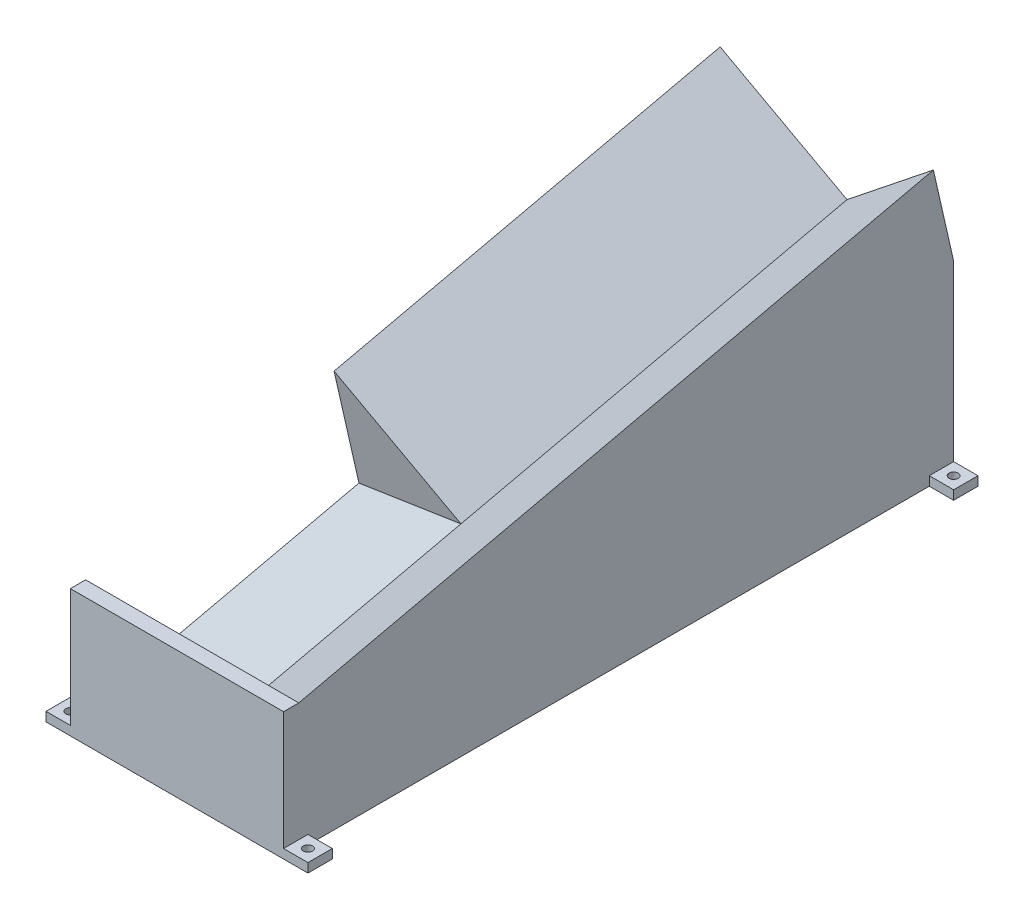
SolidWorks part; units mm, degrees
note: The reader was unsure of these and kept them because the rebuilt part matched: shared geometry of "Sketch4<3>".
ref_plane "Front Plane" through (0, 0, 0) normal (0, 0, 1) x (1, 0, 0)
ref_plane "Top Plane" through (0, 0, 0) normal (0, 1, 0) x (1, 0, 0)
ref_plane "Right Plane" through (0, 0, 0) normal (1, 0, 0) x (0, 0, -1)
sketch "Sketch3" plane through (0, 0, 0) normal (1, 0, 0) x (0, 0, -1)
  line L0 (38.5, 0) -> (-38.5, 0) construction
  line L1 (0, 0) -> (220, 0)
  line L2 (0, 0) -> (0, 10)
  line L3 (0, 10) -> (220, 10)
  line L4 (220, 0) -> (220, 10)
  line L5 (220, 10) -> (220, 60)
  line L6 (220, 60) -> (0, 10)
  line L7 (0, 38.5) -> (0, -38.5) construction
  point P6 (70, 41.2989)
  dimension "D1" = 10
  dimension "D2" = 220
  dimension "D3" = 0
  dimension "D4" = 50
extrude "Boss-Extrude2" add sketch "Sketch3" along normal blind 70 contours L5 L6 L3 | L1 L4 L3 L2
ref_plane "Plane1" through (0, 50.4912, -222.1611) normal (0, 0.2216, -0.9751) x (-1, 0, 0)
sketch "Sketch4" plane through (0, 50.4912, -222.1611) normal (0, 0.2216, -0.9751) x (-1, 0, 0)
  line L0 (-70, 9.7513) -> (-70, 39.7513)
  line L1 (-70, 39.7513) -> (-35, 9.7513)
  line L2 (-70, 9.7513) -> (0, 9.7513) construction
  line L3 (-35, 9.7513) -> (0, 39.7513)
  line L4 (0, 49.0074) -> (0, -49.0074) construction
  line L5 (0, 39.7513) -> (0, 9.7513)
  line L6 (-70, 9.7513) -> (0, 9.7513)
  dimension "D1" = 30
extrude "Boss-Extrude3" add sketch "Sketch4" against normal blind 130 contours L0 L6 L1 | L3 L6 L5
extrude "Boss-Extrude4" add sketch "Sketch4<3>" against normal blind 225 contours L0 L6 L1
sketch "Sketch4<3>" plane through (0, 50.4912, -222.1611) normal (0, 0.2216, -0.9751) x (-1, 0, 0) same geometry as "Sketch4"
sketch "Sketch7" plane through (0, 0, 0) normal (-1, 0, 0) x (0, 0, 1)
  line L0 (0, 3) -> (-220, 53) construction
  line L1 (-220, 0) -> (-220, 60) construction
  line L2 (-86.5841, 60.4432) -> (-213.3514, 89.254) construction
  line L3 (0, -38.5) -> (0, 38.5) construction
  line L4 (38.5, 0) -> (-38.5, 0) construction
  point P7 (0, 3.0122)
  dimension "D1" = 3
sketch "Sketch8" plane through (0, 50.4912, -222.1611) normal (0, 0.2216, -0.9751) x (-1, 0, 0)
  line L0 (-35, 9.7513) -> (0, 2.9254)
  line L1 (-35, 9.7513) -> (0, 9.7513)
  line L2 (0, 49.0897) -> (0, -49.0897) construction
  line L3 (-35, 9.7513) -> (0, 9.7513) construction
  line L4 (0, 9.7513) -> (0, 2.9254)
extrude "Cut-Extrude1" cut sketch "Sketch8" along normal up to surface (95.6103 mm away) from surface
sketch "Sketch9" plane through (0, 0, 0) normal (-1, 0, 0) x (0, 0, 1)
  line L0 (6.0535, 39.3892) -> (-213.3514, 89.254) construction
  line L1 (0, 0) -> (-5, 0)
  line L2 (0, 0) -> (0, 41.9014)
  line L3 (0, 41.9014) -> (-5, 41.9014)
  line L4 (-5, 0) -> (-5, 41.9014)
  dimension "D1" = 5
extrude "Boss-Extrude5" add sketch "Sketch9" against normal up to surface (70 mm away) up to face at (70, 29.8255, -92.5561)
sketch "Sketch10" plane through (0, 0, 0) normal (-1, 0, 0) x (0, 0, 1)
  line L1 (0, 0) -> (13.7086, 0)
  line L2 (0, 0) -> (0, 41.9495)
  line L3 (0, 41.9495) -> (13.7086, 41.9495)
  line L4 (13.7086, 0) -> (13.7086, 41.9495)
extrude "Cut-Extrude2" cut sketch "Sketch10" against normal through all
sketch "Sketch11" plane through (0, 0, 0) normal (0, 1, 0) x (1, 0, 0)
  line L0 (0, 0) -> (0, 220) construction
  line L1 (0, 220) -> (-8, 220)
  line L2 (0, 220) -> (0, 212)
  line L3 (0, 212) -> (-8, 212)
  line L4 (-8, 220) -> (-8, 212)
  line L5 (35, 220) -> (0, 220) construction
  line L6 (78, 220) -> (70, 220)
  line L7 (78, 220) -> (78, 212)
  line L8 (78, 212) -> (70, 212)
  line L9 (70, 220) -> (70, 212)
  line L10 (0, 8) -> (-8, 8)
  line L11 (0, 8) -> (0, 0)
  line L12 (0, 0) -> (-8, 0)
  line L13 (-8, 8) -> (-8, 0)
  line L14 (78, 8) -> (70, 8)
  line L15 (78, 8) -> (78, 0)
  line L16 (78, 0) -> (70, 0)
  line L17 (70, 8) -> (70, 0)
  line L18 (70, 0) -> (70, 5) construction
  line L19 (-38.5, 0) -> (38.5, 0) construction
  line L20 (70, 0) -> (70, 220) construction
  circle A0 centre (-4, 216) radius 1.5
  circle A1 centre (74, 216) radius 1.5
  circle A2 centre (-4, 4) radius 1.5
  circle A3 centre (74, 4) radius 1.5
  point P28 (0, 0)
  point P29 (0, 0)
  dimension "D3" = 3
  dimension "D9" = 3
  dimension "D14" = 3
  dimension "D19" = 3
  dimension "D1" = 8
  dimension "D2" = 8
  dimension "D4" = 4
  dimension "D5" = 4
  dimension "D6" = 0
  dimension "D7" = 8
  dimension "D8" = 8
  dimension "D10" = 4
  dimension "D11" = 4
  dimension "D12" = 8
  dimension "D13" = 8
  dimension "D15" = 4
  dimension "D16" = 4
  dimension "D17" = 8
  dimension "D18" = 8
  dimension "D20" = 4
  dimension "D21" = 4
extrude "Boss-Extrude6" add sketch "Sketch11" along normal blind 3
